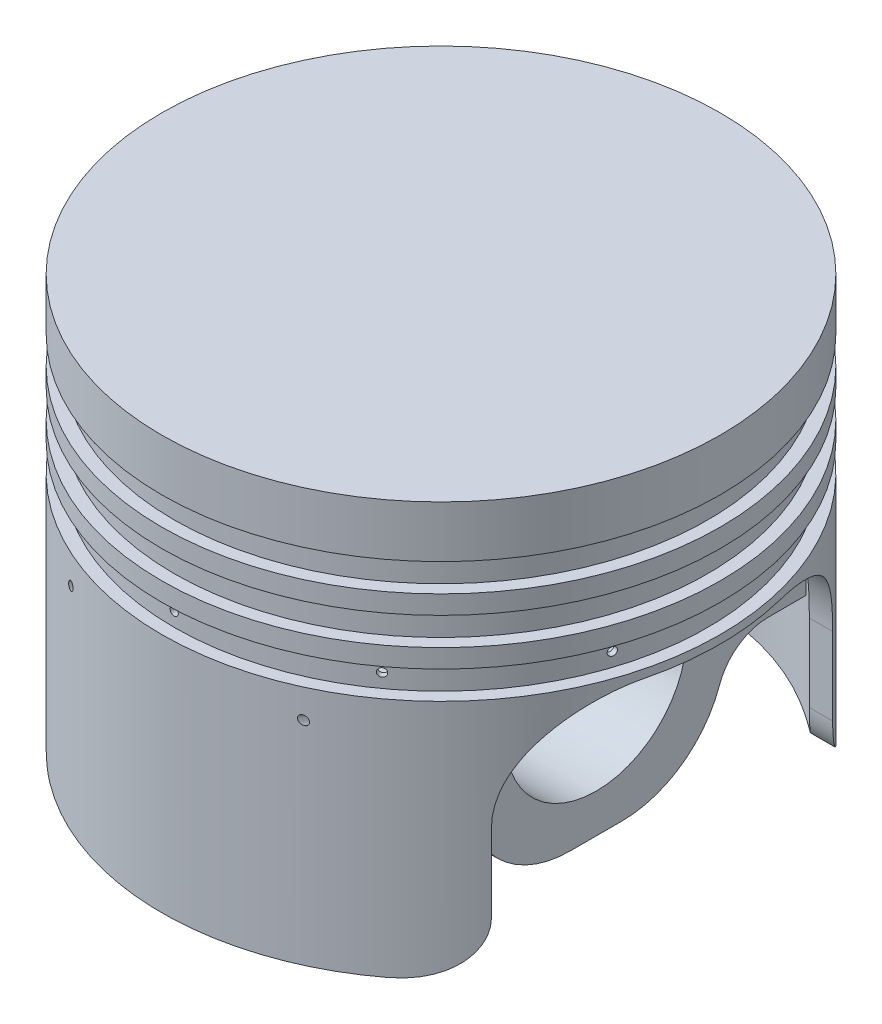
SolidWorks part; units mm, degrees
material "Aluminum, EN AC-44300, die cast, F"
ref_plane "Front Plane" through (0, 0, 0) normal (0, 0, 1) x (1, 0, 0)
ref_plane "Top Plane" through (0, 0, 0) normal (0, 1, 0) x (1, 0, 0)
ref_plane "Right Plane" through (0, 0, 0) normal (1, 0, 0) x (0, 0, -1)
sketch "Sketch4" plane through (0, 0, 0) normal (0, 0, 1) x (1, 0, 0)
  line L0 (0, 0) -> (0, -9.13)
  line L1 (0, -9.13) -> (50.5, -9.13)
  line L2 (50.5, -9.13) -> (50.5, -80)
  line L3 (50.5, -80) -> (54, -80)
  line L4 (54, -80) -> (54, 0)
  line L5 (54, 0) -> (0, 0)
  dimension "D1" = 54
  dimension "D2" = 80
  dimension "D3" = 9.13
  dimension "D4" = 3.5
revolve "Revolve2" add sketch "Sketch4" angle 360 about L0
sketch "Sketch5" plane through (0, 0, 0) normal (1, 0, 0) x (0, 0, -1)
  line L0 (-54, -80) -> (54, -80) construction
  line L1 (-33, -80) -> (33, -80)
  line L2 (-33, -80) -> (-33, -35)
  line L3 (-33, -35) -> (33, -35)
  line L4 (33, -80) -> (33, -35)
  line L5 (-33, -80) -> (33, -35) construction
  line L6 (-33, -35) -> (33, -80) construction
  point P0 (0, -57.5)
  dimension "D1" = 66
  dimension "D2" = 45
extrude "Cut-Extrude2" cut sketch "Sketch5" against normal through all both and the other way through all
sketch "Sketch6" plane through (0, 0, 0) normal (1, 0, 0) x (0, 0, -1)
  line L0 (0, 0) -> (0, -25.257) construction
  line L1 (54, -80) -> (54, 0) construction
  line L2 (51.6, -15.4) -> (56.4, -15.4)
  line L3 (51.6, -15.4) -> (51.6, -10)
  line L4 (51.6, -10) -> (56.4, -10)
  line L5 (56.4, -15.4) -> (56.4, -10)
  line L6 (51.6, -15.4) -> (56.4, -10) construction
  line L7 (51.6, -10) -> (56.4, -15.4) construction
  line L8 (54, 0) -> (-54, 0) construction
  point P3 (54, -12.7)
  dimension "D2" = 2.4
  dimension "D3" = 10
revolve "Cut-Revolve2" cut sketch "Sketch6" angle 360 about L0
pattern_linear "LPattern2" count 2 spacing 9 along (0, -1, 0) of "Cut-Revolve2"
fillet "Fillet1" radius 20 4 edges at (-40.4849, -35, 33) (-40.4849, -35, -33) (40.4849, -35, -33) (40.4849, -35, 33)
fillet "Fillet4" radius 3 1 edges at (-50.5, -9.13, 0)
ref_plane "Plane1" through (0, 0, 55) normal (0, 0, 1) x (1, 0, 0)
pattern_linear "LPattern4" count 2 spacing 9 along (0, -1, 0) of "LPattern2"
ref_plane "Plane3" through (0, 0, 43) normal (0, 0, 1) x (1, 0, 0)
sketch "Sketch19" plane through (0, -9.13, 0) normal (0, -1, 0) x (1, 0, 0)
  line L0 (0, 36.8121) -> (0, -30.3191) construction
  line L1 (30, 25) -> (15, 25)
  line L2 (-30, -25) -> (-15, -25)
  line L3 (-30, -25) -> (-30, 25)
  line L4 (-30, 25) -> (-15, 25)
  line L5 (-15, -25) -> (-15, 25)
  line L6 (-30, -25) -> (-15, 25) construction
  line L7 (-30, 25) -> (-15, -25) construction
  line L8 (15, -25) -> (15, 25)
  line L9 (30, -25) -> (15, -25)
  line L10 (30, -25) -> (30, 25)
  point P3 (-22.5, 0)
  dimension "D1" = 50
  dimension "D2" = 15
  dimension "D3" = 15
extrude "Boss-Extrude3" add sketch "Sketch19" along normal blind 70
sketch "Sketch20" plane through (-30, 0, 0) normal (-1, 0, 0) x (0, 0, 1)
  line L0 (-25, -79.13) -> (-25, -9.13) construction
  line L1 (25, -79.13) -> (-25, -79.13) construction
  circle A0 centre (0, -54.13) radius 17.5
  dimension "D1" = 35
  dimension "D2" = 25
  dimension "D3" = 25
extrude "Cut-Extrude4" cut sketch "Sketch20" against normal through all
fillet "Fillet7" radius 20 4 edges at (-22.5, -79.13, 25) (-22.5, -79.13, -25) (22.5, -79.13, -25) (22.5, -79.13, 25)
fillet "Fillet8" radius 10 4 edges at (-40.4849, -80, -33) (40.4849, -80, -33) (-40.4849, -80, 33) (40.4849, -80, 33)
sketch "Sketch22" plane through (0, 0, 43) normal (0, 0, 1) x (1, 0, 0)
  point P6 (0, -30.7)
hole_wizard "1/16 (0.0625) Diameter Hole3" positions "Sketch22" profile "Sketch23" hole size "1/16" standard "ANSI Inch"
sketch "Sketch23" plane through (0, -30.7, 43) normal (1, 0, 0) x (0, 1, 0)
  line L0 (0, 0) -> (0, 12.4769)
  line L1 (0, 12.4769) -> (0.7937, 12)
  line L2 (0.7937, 12) -> (0.7937, 0.635)
  line L3 (0.7937, 0.635) -> (1.4287, 0)
  line L5 (1.4287, 0) -> (0, 0)
  line L6 (-0.7937, 0.635) -> (-1.4287, 0) construction
  line L10 (0, 12.4769) -> (-0.7938, 12) construction
  line L11 (0, -6.35) -> (0, 107.95) construction
  dimension "Hole Dia." = 1.5875
  dimension "Hole Depth" = 12
  dimension "Near C'Sink Dia." = 2.8575
  dimension "Near C'Sink Angle" = 90
  dimension "Drill Angle" = 118
pattern_circular "CirPattern3" count 10 over 360 about axis through (0, -18, 0) along (0, 1, 0) of "1/16 (0.0625) Diameter Hole3"
sketch "Sketch24" plane through (0, 0, 25) normal (0, 0, 1) x (1, 0, 0)
  line L0 (15, -59.13) -> (15, -9.13) construction
  line L1 (30, -59.13) -> (15, -59.13)
  line L2 (30, -59.13) -> (30, -34.13)
  line L3 (30, -34.13) -> (15, -34.13)
  line L4 (15, -59.13) -> (15, -34.13)
  dimension "D1" = 25
extrude "Boss-Extrude4" add sketch "Sketch24" along normal up to next
fillet "Fillet10" radius 10 1 edges at (22.5, -59.13, 25)
fillet "Fillet11" radius 10 1 edges at (22.5, -34.13, 25)
sketch "Sketch25" plane through (0, 0, -25) normal (0, 0, -1) x (-1, 0, 0)
  line L0 (-15, -59.13) -> (-15, -9.13) construction
  line L1 (-30, -59.13) -> (-15, -59.13)
  line L2 (-30, -59.13) -> (-30, -34.13)
  line L3 (-30, -34.13) -> (-15, -34.13)
  line L4 (-15, -59.13) -> (-15, -34.13)
  dimension "D1" = 25
extrude "Boss-Extrude5" add sketch "Sketch25" along normal up to next
fillet "Fillet12" radius 10 2 edges at (22.5, -34.13, -25) (22.5, -59.13, -25)
sketch "Sketch26" plane through (0, 0, -25) normal (0, 0, -1) x (-1, 0, 0)
  line L0 (30, -59.13) -> (30, -9.13) construction
  line L1 (15, -59.13) -> (30, -59.13)
  line L2 (15, -59.13) -> (15, -34.13)
  line L3 (15, -34.13) -> (30, -34.13)
  line L4 (30, -59.13) -> (30, -34.13)
extrude "Boss-Extrude6" add sketch "Sketch26" along normal up to next
fillet "Fillet13" radius 10 2 edges at (-22.5, -34.13, -25) (-22.5, -59.13, -25)
sketch "Sketch27" plane through (0, 0, 25) normal (0, 0, 1) x (1, 0, 0)
  line L0 (-15, -59.13) -> (-15, -9.13) construction
  line L1 (-30, -59.13) -> (-15, -59.13)
  line L2 (-30, -59.13) -> (-30, -34.13)
  line L3 (-30, -34.13) -> (-15, -34.13)
  line L4 (-15, -59.13) -> (-15, -34.13)
extrude "Boss-Extrude7" add sketch "Sketch27" along normal up to next
fillet "Fillet14" radius 10 2 edges at (-22.5, -34.13, 25) (-22.5, -59.13, 25)
ref_plane "Plane9" through (0, 0, 17.5) normal (0, 0, 1) x (1, 0, 0)
sketch "Sketch38" plane through (30, 0, 0) normal (1, 0, 0) x (0, 0, -1)
  line L0 (-37.8116, -34.13) -> (-37.8116, -49.13) construction
  line L1 (-40.6233, -34.13) -> (-35, -34.13) construction
  line L2 (-37.8116, -49.13) -> (-16.7705, -49.13) construction
  circle A0 centre (0, -54.13) radius 17.5 construction
  dimension "D1" = 15
sketch "Sketch39" plane through (0, 0, 17.5) normal (0, 0, 1) x (1, 0, 0)
  point P8 (22.5, -51.4441)
ref_plane "Plane10" through (0, 0, 54) normal (0, 0, 1) x (1, 0, 0)
sketch "Sketch40" plane through (0, 0, 54) normal (0, 0, 1) x (1, 0, 0)
  line L0 (0, 0) -> (0, -37) construction
  line L1 (0, -37) -> (22.5, -37) construction
  point P3 (-22.5, -37)
  point P5 (22.5, -37)
  dimension "D1" = 37
ref_axis "Axis2" through (22.5, -51.4441, 17.5) along (0, 0.368, 0.9298)
ref_plane "Plane11" through (22.5, -37, 54) normal (0, 0.368, 0.9298) x (1, 0, 0)
sketch "Sketch42" plane through (22.5, -37, 54) normal (0, 0.368, 0.9298) x (1, 0, 0)
  circle A0 centre (0, 0) radius 0.8
  dimension "D1" = 1.6
extrude "Cut-Extrude5" cut sketch "Sketch42" against normal blind 50
mirror "Mirror1" about plane through (0, 0, 0) normal (1, 0, 0) of "Cut-Extrude5"
mirror "Mirror2" about plane through (0, 0, 0) normal (0, 0, 1) of "Mirror1"
equation "\"piston crown\"= 9.13mm"
equation "\"D3@Sketch4\"=\"piston crown\""
equation "\"Crank Radius\"= 5.33mm"
equation "\"Journal Radius\"= 31.75mm"
equation "\"Counterweight Thickness\"= 10mm"
equation "\"Bore\" = 108mm"
equation "\"Stroke\" = 86.4mm"
equation "\"t1\"= 2.4mm"
equation "\"t2\"= 5.4mm"
equation "\"b1\"= 10mm"
equation "\"b2\"= 4.7mm"
equation "\"t3\"= 5.0mm"
equation "\"t4\"= 1.5mm"
equation "\"D1@Sketch4\"=\"Bore\"/2"
equation "\"D1@Sketch6\"=\"t2\""
equation "\"D3@Sketch6\"=\"b1\""
